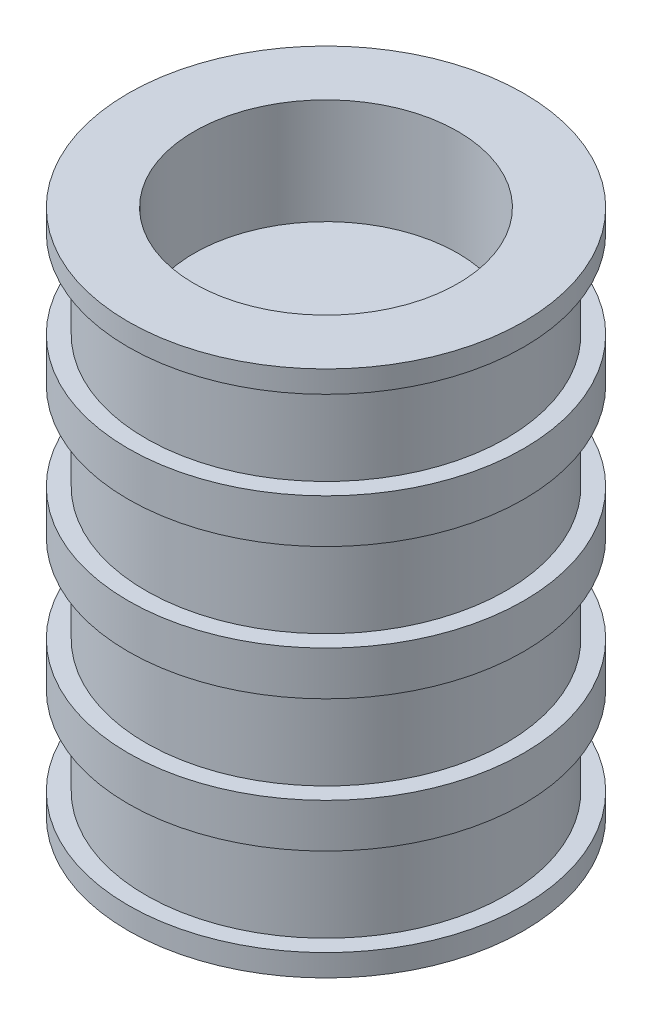
SolidWorks part; units mm, degrees
ref_plane "Front Plane" through (0, 0, 0) normal (0, 0, 1) x (1, 0, 0)
ref_plane "Top Plane" through (0, 0, 0) normal (0, 1, 0) x (1, 0, 0)
ref_plane "Right Plane" through (0, 0, 0) normal (1, 0, 0) x (0, 0, -1)
sketch "Sketch1" plane through (0, 0, 0) normal (0, 1, 0) x (1, 0, 0)
  circle A0 centre (0, 0) radius 22.5
  dimension "D1" = 45
extrude "Boss-Extrude1" add sketch "Sketch1" along normal blind 60 contours A0
sketch "Sketch2" plane through (0, 60, 0) normal (0, 1, 0) x (1, 0, 0)
  circle A0 centre (0, 0) radius 15
  dimension "D1" = 30
extrude "Cut-Extrude1" cut sketch "Sketch2" against normal blind 12
sketch "Sketch6" plane through (0, 0, 0) normal (0, 0, 1) x (1, 0, 0)
  line L0 (0, 0) -> (0, 60) construction
  line L1 (22.5, 60) -> (-22.5, 60) construction
  line L2 (0, 30) -> (-22.5, 30) construction
  line L3 (-22.5, 60) -> (-22.5, 0) construction
  line L4 (-22.5, 30) -> (-22.5, 60) construction
  line L5 (-22.5, 45) -> (0, 45) construction
  line L6 (-11.25, 45) -> (-11.25, 60) construction
  line L7 (15, 60) -> (-15, 60) construction
  line L8 (-11.25, 52.5) -> (-22.5, 52.5) construction
  line L9 (-22.5, 42.5) -> (-20.5, 42.5)
  line L10 (-22.5, 47.5) -> (-20.5, 47.5)
  line L12 (-22.5, 57.5) -> (-20.5, 57.5)
  line L13 (-20.5, 47.5) -> (-20.5, 57.5)
  line L14 (-22.5, 52.5) -> (-20.5, 57.5) construction
  line L15 (-22.5, 52.5) -> (-20.5, 47.5) construction
  line L16 (-20.5, 32.5) -> (-20.5, 42.5)
  line L17 (-22.5, 32.5) -> (-20.5, 32.5)
  line L18 (-22.5, 27.5) -> (-20.5, 27.5)
  line L19 (-20.5, 17.5) -> (-20.5, 27.5)
  line L20 (-22.5, 17.5) -> (-20.5, 17.5)
  line L21 (-22.5, 12.5) -> (-20.5, 12.5)
  line L22 (-20.5, 2.5) -> (-20.5, 12.5)
  line L23 (-22.5, 2.5) -> (-20.5, 2.5)
  line L24 (0, 0) -> (-22.5, 0) construction
  line L25 (-22.5, 57.5) -> (-22.5, 47.5)
  line L26 (-22.5, 42.5) -> (-22.5, 32.5)
  line L27 (-22.5, 27.5) -> (-22.5, 17.5)
  line L28 (-22.5, 12.5) -> (-22.5, 2.5)
  line L29 (-22.5, 57.5) -> (-22.5, 42.5) construction
  dimension "D1" = 10
  dimension "D2" = 2.5
  dimension "D3" = 2
  dimension "D5" = 2.5
  dimension "D7" = 15
  dimension "D4" = 4
  dimension "D6" = 4
revolve "Cut-Revolve1" cut sketch "Sketch6" angle 360 about L0 region at (-21.5, 37.5, 0) region at (-21.5, 52.5, 0) region at (-21.5, 22.5, 0) region at (-21.5, 7.5, 0)
